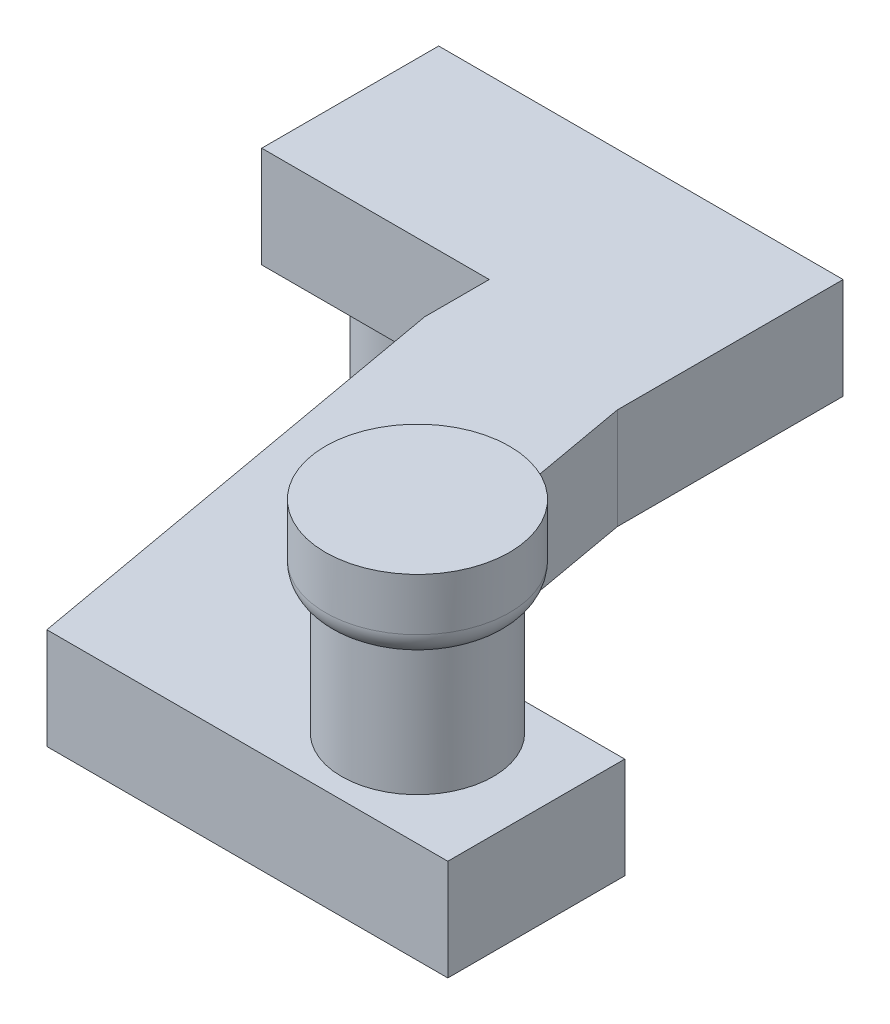
SolidWorks part; units mm, degrees
ref_plane "Front Plane" through (0, 0, 0) normal (0, 0, 1) x (1, 0, 0)
ref_plane "Top Plane" through (0, 0, 0) normal (0, 1, 0) x (1, 0, 0)
ref_plane "Right Plane" through (0, 0, 0) normal (1, 0, 0) x (0, 0, -1)
sketch "Sketch1" plane through (0, 0, 0) normal (0, 1, 0) x (1, 0, 0)
  line L0 (0, 0) -> (8, 0)
  line L1 (8, 0) -> (8, -4.4673)
  line L2 (8, -4.4673) -> (9.0546, -10.3739)
  line L3 (9.0546, -10.3739) -> (14.0546, -10.3739)
  line L4 (0, -3.5) -> (4.5, -3.5)
  line L5 (4.5, -3.5) -> (4.5, -4.7773)
  line L6 (4.5, -4.7773) -> (6.1242, -13.8739)
  line L7 (6.1242, -13.8739) -> (14.0546, -13.8739)
  line L8 (14.0546, -10.3739) -> (14.0546, -13.8739)
  line L9 (0, 0) -> (0, -3.5)
  dimension "D1" = 8
  dimension "D2" = 6
  dimension "D4" = 5
  dimension "D5" = 3.5
extrude "Boss-Extrude1" add sketch "Sketch1" along normal blind 2
sketch "Sketch2" plane through (0, 2, 0) normal (0, 1, 0) x (1, 0, 0)
  line L0 (14.0546, -10.3739) -> (9.0546, -10.3739) construction
  line L1 (14.0546, -13.8739) -> (14.0546, -10.3739) construction
  circle A0 centre (11.5546, -11.9739) radius 1.5
  dimension "D1" = 1.6
  dimension "D2" = 2.5
extrude "Boss-Extrude2" add sketch "Sketch2" along normal blind 2.5
sketch "Sketch3" plane through (0, 4.5, 0) normal (0, 1, 0) x (1, 0, 0)
  circle A0 centre (11.5546, -11.9739) radius 1.82
extrude "Boss-Extrude3" add sketch "Sketch3" along normal blind 1.5
fillet "Fillet2" radius 0.5 1 edges at (11.5546, 4.5, 13.7939)
sketch "Sketch4" plane through (0, 0, 0) normal (0, -1, 0) x (-1, 0, 0)
  circle A0 centre (-1.718, -1.4929) radius 1.4
extrude "Boss-Extrude4" add sketch "Sketch4" along normal blind 3
sketch "Sketch5" plane through (0, -3, 0) normal (0, -1, 0) x (1, 0, 0)
  circle A0 centre (1.7071, 1.4764) radius 1.7
extrude "Boss-Extrude5" add sketch "Sketch5" along normal blind 1
fillet "Fillet3" radius 0.5 1 edges at (1.7071, -3, -0.2236)
